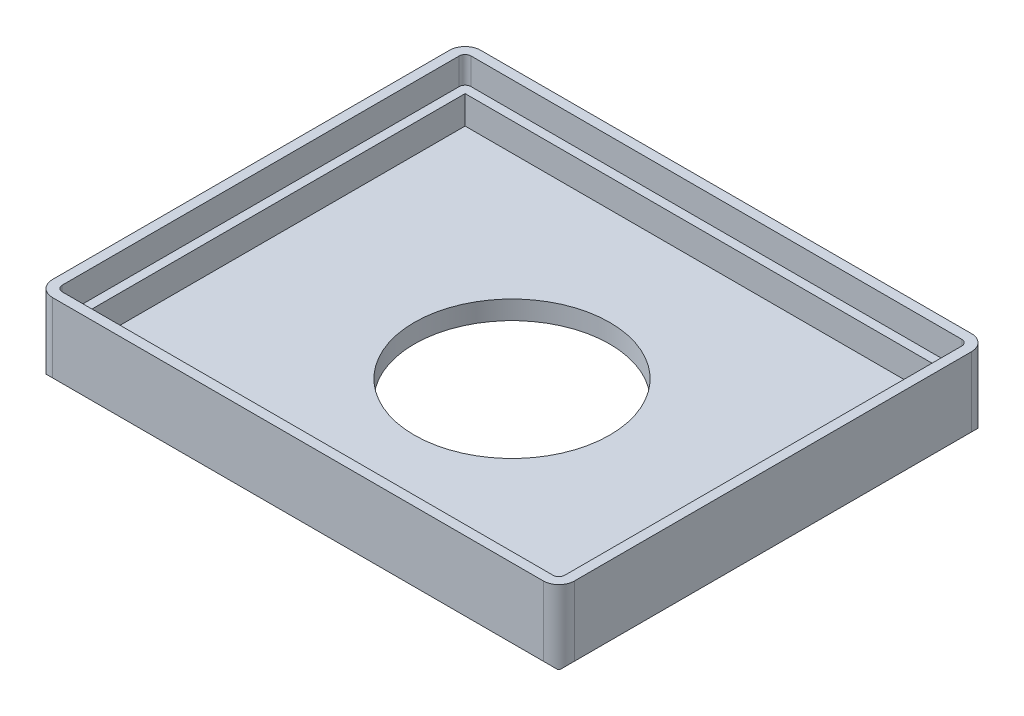
SolidWorks part; units mm, degrees
ref_plane "Front Plane" through (0, 0, 0) normal (0, 0, 1) x (1, 0, 0)
ref_plane "Top Plane" through (0, 0, 0) normal (0, 1, 0) x (1, 0, 0)
ref_plane "Right Plane" through (0, 0, 0) normal (1, 0, 0) x (0, 0, -1)
sketch "Sketch1" plane through (0, 0, 0) normal (0, 1, 0) x (1, 0, 0)
  line L1 (-33.4, 27.4) -> (33.4, 27.4)
  line L2 (-33.4, 27.4) -> (-33.4, -27.4)
  line L3 (-33.4, -27.4) -> (33.4, -27.4)
  line L4 (33.4, 27.4) -> (33.4, -27.4)
  line L5 (-33.4, 27.4) -> (33.4, -27.4) construction
  line L6 (-33.4, -27.4) -> (33.4, 27.4) construction
  point P0 (0, 0)
  dimension "D1" = 66.8
  dimension "D2" = 54.8
extrude "Boss-Extrude1" add sketch "Sketch1" along normal blind 6
chamfer "Chamfer2" distance 0.5 angle 45 4 edges at (0, 0, -27.4) (-33.4, 0, 0) (0, 0, 27.4) (33.4, 0, 0)
fillet "Fillet2" radius 2 4 edges at (33.4, 3.25, 27.4) (-33.4, 3.25, 27.4) (33.4, 3.25, -27.4) (-33.4, 3.25, -27.4)
shell "Shell3" thickness 2.4 removed face at (0, 6, 0)
sketch "Sketch5" plane through (0, 6, 0) normal (0, 1, 0) x (1, 0, 0)
  line L24 (-31.4, -26.15) -> (31.4, -26.15)
  line L25 (32.15, -25.4) -> (32.15, 25.4)
  line L26 (31.4, 26.15) -> (-31.4, 26.15)
  line L27 (-32.15, 25.4) -> (-32.15, -25.4)
  line L28 (33.4, -25.4) -> (33.4, 25.4)
  line L29 (31.4, 27.4) -> (-31.4, 27.4)
  line L30 (-31.4, -27.4) -> (31.4, -27.4)
  line L31 (-33.4, 25.4) -> (-33.4, -25.4)
  line L32 (33.4, -25.4) -> (33.4, 25.4)
  line L33 (31.4, 27.4) -> (-31.4, 27.4)
  line L34 (-31.4, -27.4) -> (31.4, -27.4)
  line L35 (-33.4, 25.4) -> (-33.4, -25.4)
  arc A21 (31.4, -26.15) -> (32.15, -25.4) centre (31.4, -25.4) ccw
  arc A22 (32.15, 25.4) -> (31.4, 26.15) centre (31.4, 25.4) ccw
  arc A23 (-31.4, 26.15) -> (-32.15, 25.4) centre (-31.4, 25.4) ccw
  arc A26 (-31.4, 27.4) -> (-33.4, 25.4) centre (-31.4, 25.4) ccw
  arc A27 (33.4, 25.4) -> (31.4, 27.4) centre (31.4, 25.4) ccw
  arc A28 (31.4, -27.4) -> (33.4, -25.4) centre (31.4, -25.4) ccw
  arc A29 (-33.4, -25.4) -> (-31.4, -27.4) centre (-31.4, -25.4) ccw
  arc A30 (-31.4, 27.4) -> (-33.4, 25.4) centre (-31.4, 25.4) ccw
  arc A31 (33.4, 25.4) -> (31.4, 27.4) centre (31.4, 25.4) ccw
  arc A32 (31.4, -27.4) -> (33.4, -25.4) centre (31.4, -25.4) ccw
  arc A33 (-33.4, -25.4) -> (-31.4, -27.4) centre (-31.4, -25.4) ccw
  arc A34 (-32.15, -25.4) -> (-31.4, -26.15) centre (-31.4, -25.4) ccw
  dimension "D1" = 0
  dimension "D2" = 1.25
extrude "Boss-Extrude4" add sketch "Sketch5" along normal blind 3.4
sketch "Sketch6" plane through (0, 0, 0) normal (0, -1, 0) x (1, 0, 0)
  circle A0 centre (0, 0) radius 12.5
  dimension "D1" = 25
extrude "Cut-Extrude2" cut sketch "Sketch6" against normal up to next
